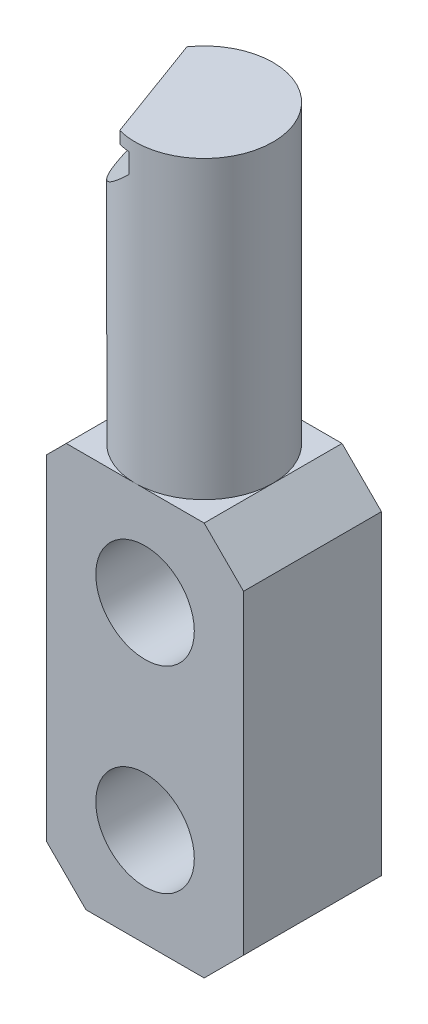
SolidWorks part; units mm, degrees
material "SUS304"
ref_plane "Front" through (0, 0, 0) normal (0, 0, 1) x (1, 0, 0)
ref_plane "Top" through (0, 0, 0) normal (0, 1, 0) x (1, 0, 0)
ref_plane "Right" through (0, 0, 0) normal (1, 0, 0) x (0, 0, -1)
sketch "Sketch1" plane through (0, 0, 0) normal (0, 0, 1) x (1, 0, 0)
  line L1 (0, 0) -> (10, 0)
  line L2 (0, 0) -> (0, 20)
  line L3 (0, 20) -> (10, 20)
  line L4 (10, 0) -> (10, 20)
  dimension "D1" = 20
  dimension "D2" = 10
extrude "Boss-Extrude1" add sketch "Sketch1" along normal blind 7
sketch "Sketch2" plane through (0, 20, 0) normal (0, 1, 0) x (1, 0, 0)
  line L0 (10, 0) -> (0, 0) construction
  line L1 (10, -7) -> (0, -7) construction
  line L2 (0, -7) -> (0, 0) construction
  circle A0 centre (4.5, -3.5) radius 3.5
  dimension "D1" = 4.5
extrude "Boss-Extrude2" add sketch "Sketch2" along normal blind 15
sketch "Sketch3" plane through (0, 0, 7) normal (0, 0, 1) x (1, 0, 0)
  line L0 (0, 20) -> (0, 0) construction
  line L1 (0, 0) -> (10, 0) construction
  circle A0 centre (5, 15) radius 2.5
  circle A1 centre (5, 5) radius 2.5
  dimension "D1" = 5
  dimension "D2" = 5
  dimension "D3" = 5
  dimension "D4" = 10
extrude "Cut-Extrude1" cut sketch "Sketch3" against normal through all
ref_plane "Plane1" through (1.6639, 0, 4.5395) normal (0.3442, 0, 0.9389) x (0.9389, 0, -0.3442)
sketch "Sketch4" plane through (1.6639, 0, 4.5395) normal (0.3442, 0, 0.9389) x (0.9389, 0, -0.3442)
  line L0 (-0.4794, 35) -> (1.0106, 35)
  line L1 (6.5206, 35) -> (-0.4794, 35) construction
  line L2 (1.0106, 35) -> (1.0106, 34.4)
  line L3 (1.0106, 34.4) -> (1.5106, 34.4)
  line L4 (1.5106, 34.4) -> (1.5106, 33.4)
  line L5 (1.5106, 33.4) -> (-0.4794, 31.266)
  line L6 (-0.4794, 35) -> (-0.4794, 20) construction
  line L7 (-0.4794, 31.266) -> (-0.4794, 35)
  line L8 (3.0206, 35) -> (3.0206, 20) construction
  dimension "D1" = 0.5
  dimension "D2" = 1.51
  dimension "D3" = 0.6
  dimension "D4" = 1
  dimension "D5" = 43
extrude "Cut-Extrude2" cut sketch "Sketch4" along normal through all and the other way through all
chamfer "Chamfer1" distance 2 angle 45 3 edges at (0, 0, 3.5) (10, 0, 3.5) (10, 20, 3.5)
chamfer "Chamfer2" distance 1 angle 45 1 edges at (0, 20, 3.5)
